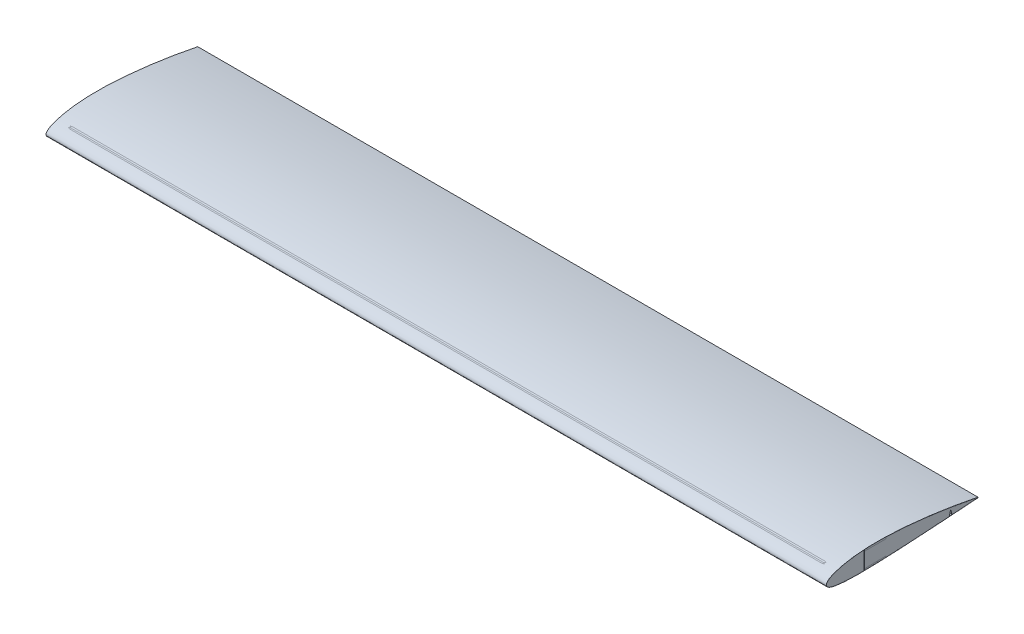
SolidWorks part; units mm, degrees
ref_plane "Front Plane" through (0, 0, 0) normal (0, 0, 1) x (1, 0, 0)
ref_plane "Top Plane" through (0, 0, 0) normal (0, 1, 0) x (1, 0, 0)
ref_plane "Right Plane" through (0, 0, 0) normal (1, 0, 0) x (0, 0, -1)
curve "Curve1"
  spline degree 3 poles (0, 25.4, 0.0064) (0, 25.2657, 0.0346) (0, 24.9974, 0.0911) (0, 24.5944, 0.1721) (0, 24.1917, 0.2509) (0, 23.7893, 0.3278) (0, 23.3874, 0.4029) (0, 22.9859, 0.4765) (0, 22.5851, 0.5485) (0, 22.1849, 0.619) (0, 21.7856, 0.688) (0, 21.3872, 0.7554) (0, 20.9898, 0.8212) (0, 20.5935, 0.8853) (0, 20.1985, 0.9476) (0, 19.8047, 1.0082) (0, 19.4123, 1.067) (0, 19.0215, 1.124) (0, 18.6322, 1.1792) (0, 18.2447, 1.2326) (0, 17.859, 1.2841) (0, 17.4751, 1.3339) (0, 17.0933, 1.382) (0, 16.7135, 1.4283) (0, 16.3359, 1.4729) (0, 15.9606, 1.5158) (0, 15.5877, 1.5571) (0, 15.2173, 1.5967) (0, 14.8494, 1.6346) (0, 14.4842, 1.6709) (0, 14.1217, 1.7054) (0, 13.7621, 1.7383) (0, 13.4054, 1.7695) (0, 13.0517, 1.7989) (0, 12.7011, 1.8265) (0, 12.3537, 1.8522) (0, 12.0097, 1.8761) (0, 11.6689, 1.8981) (0, 11.3317, 1.918) (0, 10.9979, 1.936) (0, 10.6678, 1.9519) (0, 10.3414, 1.9657) (0, 10.0188, 1.9774) (0, 9.7001, 1.9869) (0, 9.3853, 1.9942) (0, 9.0746, 1.9993) (0, 8.7679, 2.0022) (0, 8.4655, 2.0029) (0, 8.1673, 2.0014) (0, 7.8734, 1.9977) (0, 7.584, 1.9918) (0, 7.2991, 1.9837) (0, 7.0187, 1.9735) (0, 6.7429, 1.9612) (0, 6.4718, 1.9468) (0, 6.2055, 1.9304) (0, 5.944, 1.912) (0, 5.6874, 1.8917) (0, 5.4358, 1.8694) (0, 5.1892, 1.8454) (0, 4.9477, 1.8195) (0, 4.7114, 1.792) (0, 4.4802, 1.7628) (0, 4.2543, 1.7319) (0, 4.0338, 1.6995) (0, 3.8186, 1.6656) (0, 3.6089, 1.6303) (0, 3.4046, 1.5936) (0, 3.2059, 1.5556) (0, 3.0127, 1.5163) (0, 2.8252, 1.4759) (0, 2.6434, 1.4343) (0, 2.4673, 1.3917) (0, 2.297, 1.3481) (0, 2.1325, 1.3035) (0, 1.9738, 1.2581) (0, 1.8211, 1.2119) (0, 1.6742, 1.1649) (0, 1.5334, 1.1173) (0, 1.3985, 1.0691) (0, 1.2697, 1.0204) (0, 1.147, 0.9712) (0, 1.0304, 0.9215) (0, 0.9199, 0.8715) (0, 0.8155, 0.8212) (0, 0.7173, 0.7706) (0, 0.6254, 0.7198) (0, 0.5396, 0.6689) (0, 0.4601, 0.6178) (0, 0.3869, 0.5666) (0, 0.3199, 0.5153) (0, 0.2592, 0.4639) (0, 0.2049, 0.4126) (0, 0.1568, 0.3611) (0, 0.1151, 0.3097) (0, 0.0797, 0.2582) (0, 0.0507, 0.2067) (0, 0.0281, 0.1551) (0, 0.0119, 0.1034) (0, 0.0022, 0.0517) (0, -0.0011, 0.0014) (0, 0.0021, -0.0476) (0, 0.0119, -0.095) (0, 0.0281, -0.1421) (0, 0.0507, -0.1886) (0, 0.0797, -0.2345) (0, 0.1151, -0.2796) (0, 0.1568, -0.3238) (0, 0.2049, -0.3671) (0, 0.2593, -0.4092) (0, 0.32, -0.4502) (0, 0.387, -0.49) (0, 0.4602, -0.5285) (0, 0.5397, -0.5656) (0, 0.6255, -0.6013) (0, 0.7175, -0.6357) (0, 0.8157, -0.6686) (0, 0.92, -0.7001) (0, 1.0306, -0.7301) (0, 1.1472, -0.7588) (0, 1.2699, -0.786) (0, 1.3988, -0.8119) (0, 1.5336, -0.8364) (0, 1.6745, -0.8596) (0, 1.8213, -0.8815) (0, 1.974, -0.9021) (0, 2.1327, -0.9215) (0, 2.2972, -0.9397) (0, 2.4675, -0.9567) (0, 2.6436, -0.9725) (0, 2.8254, -0.9871) (0, 3.0129, -1.0006) (0, 3.206, -1.0129) (0, 3.4048, -1.0241) (0, 3.609, -1.0341) (0, 3.8188, -1.043) (0, 4.0339, -1.0507) (0, 4.2545, -1.0573) (0, 4.4804, -1.0628) (0, 4.7115, -1.0671) (0, 4.9478, -1.0703) (0, 5.1893, -1.0723) (0, 5.4359, -1.0732) (0, 5.6875, -1.073) (0, 5.9441, -1.0718) (0, 6.2056, -1.0694) (0, 6.4719, -1.0661) (0, 6.7429, -1.0617) (0, 7.0187, -1.0564) (0, 7.2991, -1.0502) (0, 7.584, -1.0431) (0, 7.8735, -1.0352) (0, 8.1673, -1.0265) (0, 8.4655, -1.017) (0, 8.7679, -1.0069) (0, 9.0746, -0.996) (0, 9.3853, -0.9846) (0, 9.7001, -0.9725) (0, 10.0188, -0.9599) (0, 10.3414, -0.9466) (0, 10.6678, -0.9328) (0, 10.9979, -0.9185) (0, 11.3316, -0.9035) (0, 11.6689, -0.888) (0, 12.0096, -0.8718) (0, 12.3537, -0.855) (0, 12.7011, -0.8375) (0, 13.0517, -0.8194) (0, 13.4053, -0.8005) (0, 13.762, -0.781) (0, 14.1217, -0.7608) (0, 14.4841, -0.7398) (0, 14.8494, -0.7181) (0, 15.2172, -0.6958) (0, 15.5877, -0.6729) (0, 15.9606, -0.6493) (0, 16.3359, -0.6253) (0, 16.7134, -0.6007) (0, 17.0932, -0.5758) (0, 17.475, -0.5506) (0, 17.8589, -0.5252) (0, 18.2446, -0.4996) (0, 18.6321, -0.4739) (0, 19.0214, -0.4481) (0, 19.4122, -0.4224) (0, 19.8046, -0.3966) (0, 20.1983, -0.3708) (0, 20.5934, -0.3449) (0, 20.9897, -0.3189) (0, 21.3871, -0.2926) (0, 21.7855, -0.2659) (0, 22.1848, -0.2386) (0, 22.585, -0.2108) (0, 22.9858, -0.1822) (0, 23.3872, -0.153) (0, 23.7892, -0.1231) (0, 24.1915, -0.0928) (0, 24.5941, -0.0626) (0, 24.997, -0.0331) (0, 25.2657, -0.0153) (0, 25.4, -0.0064) knots 0 0 0 0 0.007941 0.015868 0.023782 0.031684 0.039571 0.047444 0.055299 0.063136 0.070953 0.078747 0.086517 0.09426 0.101975 0.10966 0.117312 0.124931 0.132515 0.14006 0.147567 0.155033 0.162457 0.169836 0.17717 0.184456 0.191693 0.198879 0.206013 0.213092 0.220115 0.227081 0.233988 0.240834 0.247617 0.254336 0.260989 0.267575 0.274092 0.280538 0.286913 0.293214 0.299441 0.305592 0.311665 0.31766 0.323575 0.329409 0.33516 0.340829 0.346413 0.351912 0.357324 0.362648 0.367884 0.373031 0.378086 0.383051 0.387923 0.392702 0.397387 0.401977 0.406471 0.410868 0.415168 0.41937 0.423472 0.427475 0.431378 0.435179 0.438879 0.442477 0.445971 0.449362 0.45265 0.455833 0.458911 0.461884 0.464751 0.467513 0.470169 0.47272 0.475165 0.477504 0.479738 0.481867 0.483893 0.485816 0.487638 0.48936 0.490986 0.492517 0.493957 0.495311 0.496586 0.497786 0.498922 0.500002 0.50104 0.502047 0.503039 0.503952 0.504878 0.505831 0.506824 0.507866 0.508967 0.510136 0.51138 0.512704 0.514115 0.515615 0.517209 0.518901 0.520691 0.522584 0.524581 0.526682 0.528891 0.531207 0.533632 0.536166 0.538809 0.541562 0.544425 0.547398 0.550481 0.553673 0.556974 0.560384 0.563903 0.567529 0.571261 0.5751 0.579045 0.583094 0.587247 0.591503 0.595862 0.600321 0.60488 0.609539 0.614295 0.619148 0.624097 0.629141 0.634278 0.639507 0.644828 0.650237 0.655735 0.66132 0.666991 0.672745 0.678583 0.684501 0.690499 0.696575 0.702728 0.708956 0.715257 0.72163 0.728074 0.734587 0.741166 0.747811 0.75452 0.761292 0.768124 0.775014 0.781962 0.788966 0.796023 0.803132 0.810291 0.817498 0.824752 0.832051 0.839391 0.846773 0.854193 0.86165 0.869142 0.876666 0.884222 0.891806 0.899418 0.907055 0.914715 0.922398 0.9301 0.93782 0.945557 0.953308 0.961072 0.968847 0.97663 0.984418 0.99221 1 1 1 1
sketch "Sketch3" plane through (0, 0, 0) normal (1, 0, 0) x (0, 0, -1)
  line L1 (0, 12.7) -> (0, -12.7) construction
  line L2 (354.4824, 0.0886) -> (354.4824, -0.0886)
  line L3 (354.4824, 0) -> (0, 0) construction
  line L6 (290.9824, 0) -> (290.9824, 7.62) construction
  line L10 (290.9824, 7.62) -> (287.6544, -4.8003)
  line L11 (290.9824, 7.62) -> (294.1949, -4.3693)
  line L12 (287.6544, -4.8003) -> (290.9824, -6.35)
  line L13 (290.9824, -6.35) -> (294.1949, -4.3693)
  line L14 (290.9824, 0) -> (290.9824, -6.35) construction
  line L15 (88.9, 27.0678) -> (88.9, -14.9081) construction
  line L16 (88.9, 23.8928) -> (139.7, 23.8928)
  line L17 (139.7, 23.8928) -> (139.7, 27.5851)
  line L18 (88.9, 27.0678) -> (88.9, 23.8928)
  line L19 (355.092, 0.5833) -> (355.092, -0.6591)
  line L20 (88.9, -14.9081) -> (88.9, -11.7331)
  line L21 (88.9, -11.7331) -> (139.6922, -10.8456)
  line L22 (139.6922, -10.8456) -> (139.6922, -14.0206)
  spline S0 degree 1 poles (355.092, 0.5833) (355.092, -0.6591) knots 0 0 1 1 construction
  spline S1 degree 3 poles (354.4824, 0.0886) (352.6082, 0.483) (348.863, 1.271) (343.2392, 2.4007) (337.6192, 3.5012) (332.0035, 4.5734) (326.3937, 5.6217) (320.791, 6.6479) (313.3412, 7.9862) (302.2175, 9.9271) (289.2822, 12.0693) (276.4183, 14.0744) (265.4902, 15.6897) (251.1156, 17.6976) (236.874, 19.5167) (222.7822, 21.1545) (212.4103, 22.2822) (202.1815, 23.3173) (192.1062, 24.2587) (182.1944, 25.104) (172.456, 25.8491) (161.3668, 26.5921) (149.0219, 27.2602) (135.5235, 27.7529) (122.5206, 27.9717) (110.0426, 27.9126) (99.359, 27.6139) (90.383, 27.1766) (83.0183, 26.6917) (75.9268, 26.0988) (69.1158, 25.4036) (62.5921, 24.6121) (56.3622, 23.7307) (50.4324, 22.7661) (44.8087, 21.725) (39.4966, 20.6143) (35.2734, 19.6224) (31.3121, 18.6077) (28.3048, 17.7721) (25.414, 16.8975) (23.365, 16.2423) (21.3993, 15.5778) (19.5174, 14.9049) (17.7198, 14.2245) (16.0069, 13.5374) (14.3791, 12.8445) (12.8369, 12.1465) (11.3806, 11.4442) (10.0105, 10.7383) (8.727, 10.0294) (7.5304, 9.318) (6.4209, 8.6048) (5.3988, 7.8902) (4.4643, 7.1745) (3.6176, 6.458) (2.8589, 5.7409) (2.1883, 5.0233) (1.6061, 4.3053) (1.1124, 3.5867) (0.7076, 2.8675) (0.392, 2.1475) (0.166, 1.4266) (0.0306, 0.7051) (-0.0151, 0.0023) (0.03, -0.6811) (0.1662, -1.3427) (0.3921, -1.9994) (0.7078, -2.649) (1.1127, -3.2894) (1.6065, -3.919) (2.189, -4.5362) (2.8598, -5.1397) (3.6189, -5.728) (4.4659, -6.3001) (5.4008, -6.855) (6.4232, -7.3918) (7.533, -7.9099) (8.7299, -8.4087) (10.0137, -8.8878) (11.384, -9.3471) (12.8406, -9.7864) (14.383, -10.2059) (16.0109, -10.6056) (17.724, -10.9858) (19.5217, -11.3467) (21.4037, -11.6888) (23.3694, -12.0125) (25.4185, -12.318) (27.5503, -12.6058) (29.7644, -12.8763) (32.0603, -13.1297) (35.2816, -13.4506) (39.509, -13.8076) (44.8204, -14.1653) (50.4434, -14.4593) (56.3724, -14.6897) (62.6015, -14.8564) (69.1244, -14.9593) (75.9346, -14.999) (83.0252, -14.9771) (90.3891, -14.8962) (98.0187, -14.7598) (105.9066, -14.5724) (114.0447, -14.339) (122.4249, -14.0642) (131.0387, -13.7525) (139.8776, -13.407) (148.9326, -13.0293) (161.4123, -12.4772) (174.1486, -11.8638) (187.1282, -11.1819) (197.1228, -10.6261) (207.2759, -10.0307) (219.334, -9.2899) (231.5492, -8.5038) (243.9097, -7.6885) (254.647, -6.9749) (263.6596, -6.3774) (272.7492, -5.778) (281.9067, -5.1773) (292.9484, -4.4535) (302.1903, -3.8388) (309.6118, -3.3326) (315.196, -2.9438) (320.79, -2.5451) (326.3924, -2.1363) (332.0019, -1.7188) (337.6169, -1.2958) (343.236, -0.8748) (348.8576, -0.4618) (352.6075, -0.213) (354.4824, -0.0886) knots 0 0 0 0 0.007941 0.015868 0.023782 0.031684 0.039571 0.047444 0.055299 0.070953 0.09426 0.10966 0.124931 0.14006 0.169836 0.184456 0.198879 0.213092 0.227081 0.240834 0.254336 0.267575 0.286913 0.305592 0.323575 0.340829 0.357324 0.367884 0.378086 0.387923 0.397387 0.406471 0.415168 0.423472 0.431378 0.438879 0.445971 0.449362 0.455833 0.458911 0.461884 0.464751 0.467513 0.470169 0.47272 0.475165 0.477504 0.479738 0.481867 0.483893 0.485816 0.487638 0.48936 0.490986 0.492517 0.493957 0.495311 0.496586 0.497786 0.498922 0.500002 0.50104 0.502047 0.503039 0.503952 0.504878 0.505831 0.506824 0.507866 0.508967 0.510136 0.51138 0.512704 0.514115 0.515615 0.517209 0.518901 0.520691 0.522584 0.524581 0.526682 0.528891 0.531207 0.533632 0.536166 0.538809 0.541562 0.544425 0.547398 0.550481 0.553673 0.556974 0.563903 0.571261 0.579045 0.587247 0.595862 0.60488 0.614295 0.624097 0.634278 0.644828 0.655735 0.666991 0.678583 0.690499 0.702728 0.715257 0.728074 0.75452 0.768124 0.781962 0.796023 0.810291 0.832051 0.846773 0.86165 0.876666 0.884222 0.899418 0.914715 0.9301 0.93782 0.945557 0.953308 0.961072 0.968847 0.97663 0.984418 0.99221 1 1 1 1
  spline S2 degree 3 poles (355.092, 0.5833) (340.3127, 3.693) (310.6199, 9.2752) (265.8868, 16.4895) (228.4235, 21.2496) (198.3754, 24.3469) (175.8005, 26.2799) (153.1859, 27.7344) (130.5343, 28.5669) (111.6397, 28.5951) (96.5306, 28.1208) (85.2091, 27.4901) (73.9067, 26.5545) (62.6352, 25.2772) (51.4111, 23.6096) (42.1176, 21.8373) (34.7401, 20.1344) (29.2444, 18.6936) (23.7983, 17.061) (18.4203, 15.1959) (13.1437, 13.0326) (8.8802, 10.8891) (5.6308, 8.8467) (3.3237, 7.0865) (1.2453, 5.0033) (-0.1004, 2.8369) (-0.6183, 0.82) (-0.635, -0.7773) (-0.19, -2.3153) (0.8469, -4.1077) (2.6493, -5.87) (5.1185, -7.4554) (7.7371, -8.698) (11.3328, -10.0346) (15.9372, -11.2769) (21.5293, -12.3685) (27.1547, -13.1959) (32.7972, -13.8378) (40.3339, -14.5078) (49.7691, -15.075) (61.0997, -15.4585) (72.4323, -15.615) (83.7634, -15.5946) (95.0915, -15.437) (109.9642, -15.0928) (122.9439, -14.664) (135.9206, -14.1746) (143.6903, -13.8607) (157.1163, -13.285) (174.3107, -12.4807) (196.9278, -11.2693) (227.0713, -9.4426) (257.1966, -7.4054) (287.3245, -5.4343) (309.9221, -3.947) (332.5149, -2.3034) (347.562, -1.1587) (355.092, -0.6591) knots -0.000684 -0.000684 -0.000684 -0.000684 0.061908 0.1245 0.187092 0.218388 0.249684 0.28098 0.312276 0.343572 0.35922 0.374868 0.390516 0.406164 0.421812 0.43746 0.445284 0.453108 0.460932 0.468756 0.47658 0.484404 0.488316 0.492228 0.49614 0.500052 0.502008 0.503964 0.50592 0.507876 0.511788 0.5157 0.519612 0.523524 0.531348 0.539172 0.546996 0.55482 0.562644 0.578292 0.59394 0.609588 0.625236 0.640884 0.656532 0.68689 0.694714 0.710362 0.719124 0.75042 0.781716 0.813012 0.875604 0.9069 0.938196 0.969492 1.000788 1.000788 1.000788 1.000788
  point P7 (0, 0)
  point P9 (290.9824, 0)
  dimension "D1" = 354.4824
  dimension "D2" = 63.5
  dimension "D3" = 15
  dimension "D4" = 15
  dimension "D5" = 7.62
  dimension "D6" = 6.35
  dimension "D7" = 88.9
  dimension "D8" = 50.8
  dimension "D9" = 3.175
  dimension "D11" = 3.175
  dimension "D10" = 0.6096
extrude "Boss-Extrude1" add sketch "Sketch3" along normal mid plane 1828.8 contours S1 L2
sketch "Sketch4" plane through (914.4, 0, 0) normal (1, 0, 0) x (0, 0, -1)
  line L0 (88.9, -14.9081) -> (88.9, -11.7331) construction
  line L1 (88.9, -11.7331) -> (139.6922, -10.8456) construction
  line L2 (139.6922, -10.8456) -> (139.6922, -14.0206) construction
  line L3 (139.7, 23.8928) -> (139.7, 27.5851) construction
  line L4 (88.9, 27.0678) -> (88.9, 23.8928) construction
  line L5 (88.9, 23.8928) -> (139.7, 23.8928) construction
  line L6 (88.9, -14.9081) -> (88.9, -11.7331)
  line L7 (88.9, -11.7331) -> (139.6922, -10.8456)
  line L8 (139.6922, -10.8456) -> (139.6922, -14.0206)
  line L9 (139.7, 23.8928) -> (139.7, 27.5851)
  line L10 (88.9, 27.0678) -> (88.9, 23.8928)
  line L11 (88.9, 23.8928) -> (139.7, 23.8928)
split "Split1" trim tools "Sketch4" bodies to split 101 resulting bodies 103 104 105
sketch "Sketch5" plane through (914.4, 0, 0) normal (1, 0, 0) x (0, 0, -1)
  line L1 (88.9, 27.0678) -> (88.2904, 27.0678)
  line L2 (88.9, 27.0678) -> (88.9, -14.9081)
  line L3 (88.9, -14.9081) -> (88.2904, -14.9081)
  line L4 (88.2904, 27.0678) -> (88.2904, -14.9081)
  point P5 (0, 0)
  dimension "D1" = 0.6096
extrude "Cut-Extrude2" cut sketch "Sketch5" against normal through all and the other way through all
sketch "Sketch6" plane through (0, 0, 0) normal (1, 0, 0) x (0, 0, -1)
  line L0 (355.092, 0.5833) -> (355.092, -0.6591) construction
  line L1 (354.4824, 0.0886) -> (354.4824, -0.0886) construction
  line L2 (355.092, 0.5833) -> (355.092, -0.6591)
  line L3 (354.4824, 0.0886) -> (354.4824, -0.0886)
  spline S0 degree 3 poles (870.6222, -1858.9968) (960.0469, -203.7935) (629.2465, -42.1109) (265.8868, 16.4895) (228.4235, 21.2496) (198.3754, 24.3469) (175.8005, 26.2799) (153.1859, 27.7344) (130.5343, 28.5669) (111.6397, 28.5951) (96.5306, 28.1208) (85.2091, 27.4901) (73.9067, 26.5545) (62.6352, 25.2772) (51.4111, 23.6096) (42.1176, 21.8373) (34.7401, 20.1344) (29.2444, 18.6936) (23.7983, 17.061) (18.4203, 15.1959) (13.1437, 13.0326) (8.8802, 10.8891) (5.6308, 8.8467) (3.3237, 7.0865) (1.2453, 5.0033) (-0.1004, 2.8369) (-0.6183, 0.82) (-0.635, -0.7773) (-0.19, -2.3153) (0.8469, -4.1077) (2.6493, -5.87) (5.1185, -7.4554) (7.7371, -8.698) (11.3328, -10.0346) (15.9372, -11.2769) (21.5293, -12.3685) (27.1547, -13.1959) (32.7972, -13.8378) (40.3339, -14.5078) (49.7691, -15.075) (61.0997, -15.4585) (72.4323, -15.615) (83.7634, -15.5946) (95.0915, -15.437) (109.9642, -15.0928) (122.9439, -14.664) (135.9206, -14.1746) (143.6903, -13.8607) (157.1163, -13.285) (174.3107, -12.4807) (196.9278, -11.2693) (227.0713, -9.4426) (257.1966, -7.4054) (287.3245, -5.4343) (309.9221, -3.947) (535.736, 12.4814) (750.9184, 38.639) (1178.4199, -1790.42) knots -1.338181 -1.338181 -1.338181 -1.338181 0.061908 0.1245 0.187092 0.218388 0.249684 0.28098 0.312276 0.343572 0.35922 0.374868 0.390516 0.406164 0.421812 0.43746 0.445284 0.453108 0.460932 0.468756 0.47658 0.484404 0.488316 0.492228 0.49614 0.500052 0.502008 0.503964 0.50592 0.507876 0.511788 0.5157 0.519612 0.523524 0.531348 0.539172 0.546996 0.55482 0.562644 0.578292 0.59394 0.609588 0.625236 0.640884 0.656532 0.68689 0.694714 0.710362 0.719124 0.75042 0.781716 0.813012 0.875604 0.9069 0.938196 0.969492 1.845306 1.845306 1.845306 1.845306 only from (355.092, 0.5833) to (355.092, -0.6591) construction
  spline S1 degree 3 poles (1091.9556, 1847.7027) (573.6184, -79.0126) (462.8461, -21.626) (343.2392, 2.4007) (337.6192, 3.5012) (332.0035, 4.5734) (326.3937, 5.6217) (320.791, 6.6479) (313.3412, 7.9862) (302.2175, 9.9271) (289.2822, 12.0693) (276.4183, 14.0744) (265.4902, 15.6897) (251.1156, 17.6976) (236.874, 19.5167) (222.7822, 21.1545) (212.4103, 22.2822) (202.1815, 23.3173) (192.1062, 24.2587) (182.1944, 25.104) (172.456, 25.8491) (161.3668, 26.5921) (149.0219, 27.2602) (135.5235, 27.7529) (122.5206, 27.9717) (110.0426, 27.9126) (99.359, 27.6139) (90.383, 27.1766) (83.0183, 26.6917) (75.9268, 26.0988) (69.1158, 25.4036) (62.5921, 24.6121) (56.3622, 23.7307) (50.4324, 22.7661) (44.8087, 21.725) (39.4966, 20.6143) (35.2734, 19.6224) (31.3121, 18.6077) (28.3048, 17.7721) (25.414, 16.8975) (23.365, 16.2423) (21.3993, 15.5778) (19.5174, 14.9049) (17.7198, 14.2245) (16.0069, 13.5374) (14.3791, 12.8445) (12.8369, 12.1465) (11.3806, 11.4442) (10.0105, 10.7383) (8.727, 10.0294) (7.5304, 9.318) (6.4209, 8.6048) (5.3988, 7.8902) (4.4643, 7.1745) (3.6176, 6.458) (2.8589, 5.7409) (2.1883, 5.0233) (1.6061, 4.3053) (1.1124, 3.5867) (0.7076, 2.8675) (0.392, 2.1475) (0.166, 1.4266) (0.0306, 0.7051) (-0.0151, 0.0023) (0.03, -0.6811) (0.1662, -1.3427) (0.3921, -1.9994) (0.7078, -2.649) (1.1127, -3.2894) (1.6065, -3.919) (2.189, -4.5362) (2.8598, -5.1397) (3.6189, -5.728) (4.4659, -6.3001) (5.4008, -6.855) (6.4232, -7.3918) (7.533, -7.9099) (8.7299, -8.4087) (10.0137, -8.8878) (11.384, -9.3471) (12.8406, -9.7864) (14.383, -10.2059) (16.0109, -10.6056) (17.724, -10.9858) (19.5217, -11.3467) (21.4037, -11.6888) (23.3694, -12.0125) (25.4185, -12.318) (27.5503, -12.6058) (29.7644, -12.8763) (32.0603, -13.1297) (35.2816, -13.4506) (39.509, -13.8076) (44.8204, -14.1653) (50.4434, -14.4593) (56.3724, -14.6897) (62.6015, -14.8564) (69.1244, -14.9593) (75.9346, -14.999) (83.0252, -14.9771) (90.3891, -14.8962) (98.0187, -14.7598) (105.9066, -14.5724) (114.0447, -14.339) (122.4249, -14.0642) (131.0387, -13.7525) (139.8776, -13.407) (148.9326, -13.0293) (161.4123, -12.4772) (174.1486, -11.8638) (187.1282, -11.1819) (197.1228, -10.6261) (207.2759, -10.0307) (219.334, -9.2899) (231.5492, -8.5038) (243.9097, -7.6885) (254.647, -6.9749) (263.6596, -6.3774) (272.7492, -5.778) (281.9067, -5.1773) (292.9484, -4.4535) (302.1903, -3.8388) (309.6118, -3.3326) (315.196, -2.9438) (320.79, -2.5451) (326.3924, -2.1363) (332.0019, -1.7188) (337.6169, -1.2958) (343.236, -0.8748) (473.2977, 8.6816) (603.6528, -13.0399) (592.3902, 1973.3971) knots -0.482017 -0.482017 -0.482017 -0.482017 0.007941 0.015868 0.023782 0.031684 0.039571 0.047444 0.055299 0.070953 0.09426 0.10966 0.124931 0.14006 0.169836 0.184456 0.198879 0.213092 0.227081 0.240834 0.254336 0.267575 0.286913 0.305592 0.323575 0.340829 0.357324 0.367884 0.378086 0.387923 0.397387 0.406471 0.415168 0.423472 0.431378 0.438879 0.445971 0.449362 0.455833 0.458911 0.461884 0.464751 0.467513 0.470169 0.47272 0.475165 0.477504 0.479738 0.481867 0.483893 0.485816 0.487638 0.48936 0.490986 0.492517 0.493957 0.495311 0.496586 0.497786 0.498922 0.500002 0.50104 0.502047 0.503039 0.503952 0.504878 0.505831 0.506824 0.507866 0.508967 0.510136 0.51138 0.512704 0.514115 0.515615 0.517209 0.518901 0.520691 0.522584 0.524581 0.526682 0.528891 0.531207 0.533632 0.536166 0.538809 0.541562 0.544425 0.547398 0.550481 0.553673 0.556974 0.563903 0.571261 0.579045 0.587247 0.595862 0.60488 0.614295 0.624097 0.634278 0.644828 0.655735 0.666991 0.678583 0.690499 0.702728 0.715257 0.728074 0.75452 0.768124 0.781962 0.796023 0.810291 0.832051 0.846773 0.86165 0.876666 0.884222 0.899418 0.914715 0.9301 0.93782 0.945557 0.953308 0.961072 0.968847 0.97663 0.984418 0.99221 1.517326 1.517326 1.517326 1.517326 only from (354.4824, 0.0886) to (354.4824, -0.0886) construction
  spline S2 degree 3 poles (355.092, 0.5833) (340.3127, 3.693) (310.6199, 9.2752) (265.8868, 16.4895) (228.4235, 21.2496) (198.3754, 24.3469) (175.8005, 26.2799) (153.1859, 27.7344) (130.5343, 28.5669) (111.6397, 28.5951) (96.5306, 28.1208) (85.2091, 27.4901) (73.9067, 26.5545) (62.6352, 25.2772) (51.4111, 23.6096) (42.1176, 21.8373) (34.7401, 20.1344) (29.2444, 18.6936) (23.7983, 17.061) (18.4203, 15.1959) (13.1437, 13.0326) (8.8802, 10.8891) (5.6308, 8.8467) (3.3237, 7.0865) (1.2453, 5.0033) (-0.1004, 2.8369) (-0.6183, 0.82) (-0.635, -0.7773) (-0.19, -2.3153) (0.8469, -4.1077) (2.6493, -5.87) (5.1185, -7.4554) (7.7371, -8.698) (11.3328, -10.0346) (15.9372, -11.2769) (21.5293, -12.3685) (27.1547, -13.1959) (32.7972, -13.8378) (40.3339, -14.5078) (49.7691, -15.075) (61.0997, -15.4585) (72.4323, -15.615) (83.7634, -15.5946) (95.0915, -15.437) (109.9642, -15.0928) (122.9439, -14.664) (135.9206, -14.1746) (143.6903, -13.8607) (157.1163, -13.285) (174.3107, -12.4807) (196.9278, -11.2693) (227.0713, -9.4426) (257.1966, -7.4054) (287.3245, -5.4343) (309.9221, -3.947) (332.5149, -2.3034) (347.562, -1.1587) (355.092, -0.6591) knots -0.000684 -0.000684 -0.000684 -0.000684 0.061908 0.1245 0.187092 0.218388 0.249684 0.28098 0.312276 0.343572 0.35922 0.374868 0.390516 0.406164 0.421812 0.43746 0.445284 0.453108 0.460932 0.468756 0.47658 0.484404 0.488316 0.492228 0.49614 0.500052 0.502008 0.503964 0.50592 0.507876 0.511788 0.5157 0.519612 0.523524 0.531348 0.539172 0.546996 0.55482 0.562644 0.578292 0.59394 0.609588 0.625236 0.640884 0.656532 0.68689 0.694714 0.710362 0.719124 0.75042 0.781716 0.813012 0.875604 0.9069 0.938196 0.969492 1.000788 1.000788 1.000788 1.000788
  spline S3 degree 3 poles (354.4824, 0.0886) (352.6082, 0.483) (348.863, 1.271) (343.2392, 2.4007) (337.6192, 3.5012) (332.0035, 4.5734) (326.3937, 5.6217) (320.791, 6.6479) (313.3412, 7.9862) (302.2175, 9.9271) (289.2822, 12.0693) (276.4183, 14.0744) (265.4902, 15.6897) (251.1156, 17.6976) (236.874, 19.5167) (222.7822, 21.1545) (212.4103, 22.2822) (202.1815, 23.3173) (192.1062, 24.2587) (182.1944, 25.104) (172.456, 25.8491) (161.3668, 26.5921) (149.0219, 27.2602) (135.5235, 27.7529) (122.5206, 27.9717) (110.0426, 27.9126) (99.359, 27.6139) (90.383, 27.1766) (83.0183, 26.6917) (75.9268, 26.0988) (69.1158, 25.4036) (62.5921, 24.6121) (56.3622, 23.7307) (50.4324, 22.7661) (44.8087, 21.725) (39.4966, 20.6143) (35.2734, 19.6224) (31.3121, 18.6077) (28.3048, 17.7721) (25.414, 16.8975) (23.365, 16.2423) (21.3993, 15.5778) (19.5174, 14.9049) (17.7198, 14.2245) (16.0069, 13.5374) (14.3791, 12.8445) (12.8369, 12.1465) (11.3806, 11.4442) (10.0105, 10.7383) (8.727, 10.0294) (7.5304, 9.318) (6.4209, 8.6048) (5.3988, 7.8902) (4.4643, 7.1745) (3.6176, 6.458) (2.8589, 5.7409) (2.1883, 5.0233) (1.6061, 4.3053) (1.1124, 3.5867) (0.7076, 2.8675) (0.392, 2.1475) (0.166, 1.4266) (0.0306, 0.7051) (-0.0151, 0.0023) (0.03, -0.6811) (0.1662, -1.3427) (0.3921, -1.9994) (0.7078, -2.649) (1.1127, -3.2894) (1.6065, -3.919) (2.189, -4.5362) (2.8598, -5.1397) (3.6189, -5.728) (4.4659, -6.3001) (5.4008, -6.855) (6.4232, -7.3918) (7.533, -7.9099) (8.7299, -8.4087) (10.0137, -8.8878) (11.384, -9.3471) (12.8406, -9.7864) (14.383, -10.2059) (16.0109, -10.6056) (17.724, -10.9858) (19.5217, -11.3467) (21.4037, -11.6888) (23.3694, -12.0125) (25.4185, -12.318) (27.5503, -12.6058) (29.7644, -12.8763) (32.0603, -13.1297) (35.2816, -13.4506) (39.509, -13.8076) (44.8204, -14.1653) (50.4434, -14.4593) (56.3724, -14.6897) (62.6015, -14.8564) (69.1244, -14.9593) (75.9346, -14.999) (83.0252, -14.9771) (90.3891, -14.8962) (98.0187, -14.7598) (105.9066, -14.5724) (114.0447, -14.339) (122.4249, -14.0642) (131.0387, -13.7525) (139.8776, -13.407) (148.9326, -13.0293) (161.4123, -12.4772) (174.1486, -11.8638) (187.1282, -11.1819) (197.1228, -10.6261) (207.2759, -10.0307) (219.334, -9.2899) (231.5492, -8.5038) (243.9097, -7.6885) (254.647, -6.9749) (263.6596, -6.3774) (272.7492, -5.778) (281.9067, -5.1773) (292.9484, -4.4535) (302.1903, -3.8388) (309.6118, -3.3326) (315.196, -2.9438) (320.79, -2.5451) (326.3924, -2.1363) (332.0019, -1.7188) (337.6169, -1.2958) (343.236, -0.8748) (348.8576, -0.4618) (352.6075, -0.213) (354.4824, -0.0886) knots 0 0 0 0 0.007941 0.015868 0.023782 0.031684 0.039571 0.047444 0.055299 0.070953 0.09426 0.10966 0.124931 0.14006 0.169836 0.184456 0.198879 0.213092 0.227081 0.240834 0.254336 0.267575 0.286913 0.305592 0.323575 0.340829 0.357324 0.367884 0.378086 0.387923 0.397387 0.406471 0.415168 0.423472 0.431378 0.438879 0.445971 0.449362 0.455833 0.458911 0.461884 0.464751 0.467513 0.470169 0.47272 0.475165 0.477504 0.479738 0.481867 0.483893 0.485816 0.487638 0.48936 0.490986 0.492517 0.493957 0.495311 0.496586 0.497786 0.498922 0.500002 0.50104 0.502047 0.503039 0.503952 0.504878 0.505831 0.506824 0.507866 0.508967 0.510136 0.51138 0.512704 0.514115 0.515615 0.517209 0.518901 0.520691 0.522584 0.524581 0.526682 0.528891 0.531207 0.533632 0.536166 0.538809 0.541562 0.544425 0.547398 0.550481 0.553673 0.556974 0.563903 0.571261 0.579045 0.587247 0.595862 0.60488 0.614295 0.624097 0.634278 0.644828 0.655735 0.666991 0.678583 0.690499 0.702728 0.715257 0.728074 0.75452 0.768124 0.781962 0.796023 0.810291 0.832051 0.846773 0.86165 0.876666 0.884222 0.899418 0.914715 0.9301 0.93782 0.945557 0.953308 0.961072 0.968847 0.97663 0.984418 0.99221 1 1 1 1
extrude "Boss-Extrude3" add sketch "Sketch3<4>" along normal mid plane 1828.8 separate body contours S1 L2 | S2 L19
sketch "Sketch3<4>" plane through (0, 0, 0) normal (1, 0, 0) x (0, 0, -1) same geometry as "Sketch3"
extrude "Cut-Extrude1" cut sketch "Sketch3<3>" against normal through all both and the other way through all contours L12 L13 L11 L10
sketch "Sketch3<3>" plane through (0, 0, 0) normal (1, 0, 0) x (0, 0, -1) same geometry as "Sketch3"
sketch "Sketch7" plane through (0, 0, 0) normal (0, 1, 0) x (1, 0, 0)
  line L0 (914.4, 88.2904) -> (-914.4, 88.2904) construction
  line L1 (0, -0.6093) -> (0, 355.092) construction
  line L2 (279.4, 139.6922) -> (368.3, 139.6922)
  line L3 (279.4, 139.6922) -> (279.4, 190.4922)
  line L4 (279.4, 190.4922) -> (368.3, 190.4922)
  line L5 (368.3, 139.6922) -> (368.3, 190.4922)
  line L6 (914.4, 88.9) -> (914.4, 139.7) construction
  line L7 (590.4, 139.6922) -> (660.4, 139.6922)
  line L8 (590.4, 139.6922) -> (590.4, 199.6922)
  line L9 (590.4, 199.6922) -> (660.4, 199.6922)
  line L10 (660.4, 139.6922) -> (660.4, 199.6922)
  line L11 (914.4, 139.6922) -> (-914.4, 139.6922) construction
  line L12 (158.75, 139.6922) -> (158.75, 199.6922)
  line L13 (158.75, 199.6922) -> (228.75, 199.6922)
  line L14 (228.75, 139.6922) -> (228.75, 199.6922)
  line L15 (158.75, 139.6922) -> (228.75, 139.6922)
  line L16 (0, -24.3155) -> (0, 24.3155) construction
  line L17 (-158.75, 139.6922) -> (-158.75, 199.6922)
  line L18 (-158.75, 199.6922) -> (-228.75, 199.6922)
  line L19 (-368.3, 139.6922) -> (-368.3, 190.4922)
  line L20 (-228.75, 139.6922) -> (-228.75, 199.6922)
  line L21 (-158.75, 139.6922) -> (-228.75, 139.6922)
  line L22 (-279.4, 190.4922) -> (-368.3, 190.4922)
  line L23 (-279.4, 139.6922) -> (-279.4, 190.4922)
  line L24 (-279.4, 139.6922) -> (-368.3, 139.6922)
  line L25 (-590.4, 139.6922) -> (-660.4, 139.6922)
  line L26 (-660.4, 139.6922) -> (-660.4, 199.6922)
  line L27 (-590.4, 199.6922) -> (-660.4, 199.6922)
  line L28 (-590.4, 139.6922) -> (-590.4, 199.6922)
  dimension "D1" = 279.4
  dimension "D2" = 88.9
  dimension "D3" = 50.8
  dimension "D4" = 254
  dimension "D5" = 70
  dimension "D6" = 60
  dimension "D8" = 158.75
  dimension "D7" = 2
extrude "Cut-Extrude3" cut sketch "Sketch7" along normal blind 30 from offset 15.24 offset against normal yes
